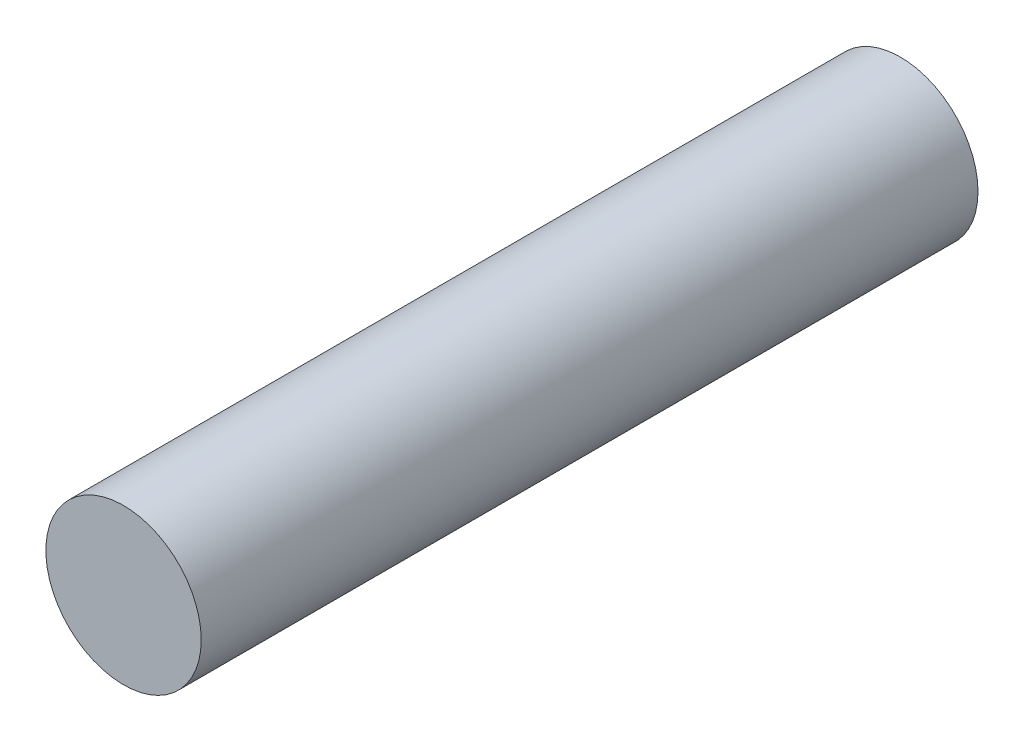
SolidWorks part; units mm, degrees
ref_plane "Front Plane"
ref_plane "Top Plane" through (0, 0, 0) normal (0, 1, 0) x (1, 0, 0)
ref_plane "Right Plane" through (0, 0, 0) normal (1, 0, 0) x (0, 0, -1)
sketch "Sketch1" plane through (0, 0, 0) normal (0, 0, 1) x (1, 0, 0)
  circle A0 centre (0, 0) radius 25.4
  dimension "D1" = 50.8
extrude "Boss-Extrude1" add sketch "Sketch1" along normal blind 127 and the other way blind 127
